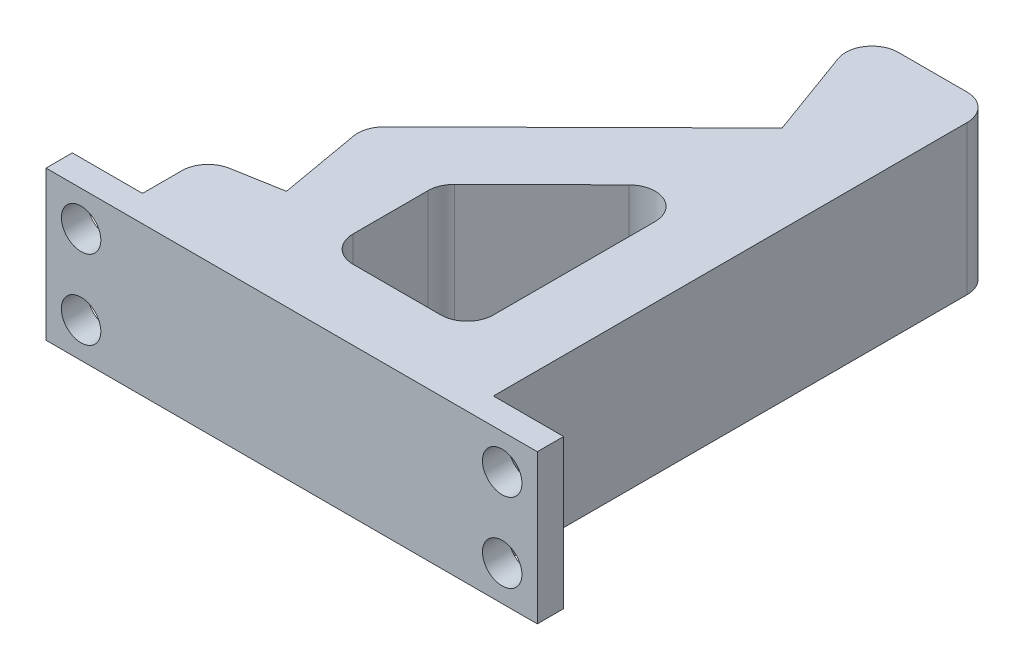
SolidWorks part; units mm, degrees
ref_plane "Front Plane" through (0, 0, 0) normal (0, 0, 1) x (1, 0, 0)
ref_plane "Top Plane" through (0, 0, 0) normal (0, 1, 0) x (1, 0, 0)
ref_plane "Right Plane" through (0, 0, 0) normal (1, 0, 0) x (0, 0, -1)
sketch "Sketch1" plane through (0, 0, 0) normal (0, 1, 0) x (1, 0, 0)
  line L0 (0, 0) -> (0, 10)
  line L1 (0, 0) -> (40, 0)
  line L2 (40, 0) -> (40, 60)
  line L3 (40, 60) -> (24.8697, 60)
  line L4 (24.8697, 60) -> (30, 45.9046)
  line L6 (30, 45.9046) -> (6.0899, 22.2435)
  line L7 (6.0899, 22.2435) -> (8, 11.4106)
  line L8 (8, 11.4106) -> (0, 10)
  line L9 (16, 8) -> (32, 8)
  line L10 (32, 8) -> (32, 36.6288)
  line L11 (32, 36.6288) -> (16, 20.7955)
  line L12 (16, 20.7955) -> (16, 8)
  dimension "D1" = 40
  dimension "D2" = 60
  dimension "D3" = 70
  dimension "D4" = 100
  dimension "D5" = 10
  dimension "D6" = 11
  dimension "D7" = 15
  dimension "D8" = 10
  dimension "D9" = 8
  dimension "D10" = 8
  dimension "D11" = 8
  dimension "D12" = 8
  dimension "D13" = 8
extrude "Boss-Extrude1" add sketch "Sketch1" along normal mid plane 17
fillet "Fillet1" radius 3 8 edges at (40, 0, -60) (16, 0, -8) (16, 0, -20.7955) (32, 0, -36.6288) (32, 0, -8) (0, 0, -10) (6.0899, 0, -22.2435) (24.8697, 0, -60)
sketch "Sketch2" plane through (0, 8.5, 0) normal (0, 1, 0) x (1, 0, 0)
  line L1 (0, 0) -> (-8, 0)
  line L2 (0, 0) -> (0, 3)
  line L3 (0, 3) -> (-8, 3)
  line L4 (-8, 0) -> (-8, 3)
  line L5 (40, 0) -> (48, 0)
  line L6 (40, 0) -> (40, 3)
  line L7 (40, 3) -> (48, 3)
  line L8 (48, 0) -> (48, 3)
  dimension "D1" = 3
  dimension "D2" = 8
  dimension "D3" = 8
extrude "Boss-Extrude2" add sketch "Sketch2" against normal up to surface (17 mm away) up to face at (18.7706, -8.5, -29.5137)
sketch "Sketch3" plane through (0, 0, -3) normal (0, 0, -1) x (-1, 0, 0)
  line L0 (0, 8.5) -> (8, 8.5) construction
  line L1 (8, -8.5) -> (0, -8.5) construction
  line L2 (-40, -8.5) -> (-40, 8.5) construction
  line L3 (0, -8.5) -> (0, 8.5) construction
  circle A0 centre (4, -4.5) radius 2.25
  circle A1 centre (4, 4.5) radius 2.25
  circle A2 centre (-44, 4.5) radius 2.25
  circle A3 centre (-44, -4.5) radius 2.25
  point P12 (0, 0)
  point P13 (0, 0)
  point P18 (0, 0)
  point P19 (0, 0)
  point P20 (0, 0)
  dimension "D1" = 4.5
  dimension "D2" = 4.5
  dimension "D3" = 4.5
  dimension "D4" = 4.5
  dimension "D5" = 4
  dimension "D6" = 4
  dimension "D7" = 4
  dimension "D8" = 4
extrude "Cut-Extrude1" cut sketch "Sketch3" against normal through all
